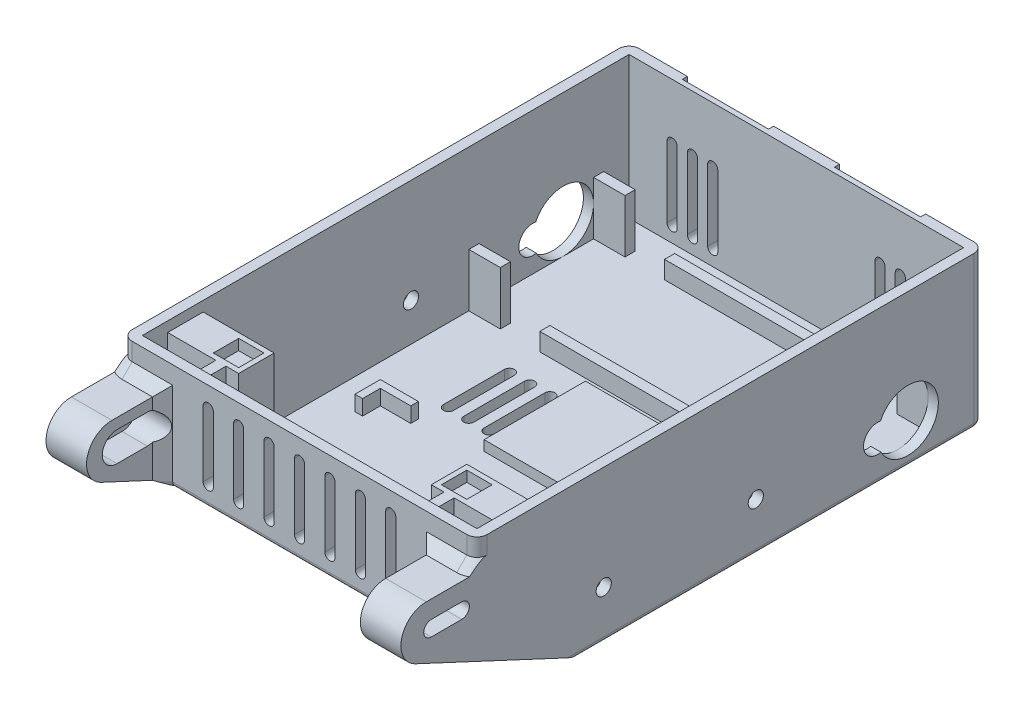
SolidWorks part; units mm, degrees
ref_plane "Ebene vorne" through (0, 0, 0) normal (0, 0, 1) x (1, 0, 0)
ref_plane "Ebene oben" through (0, 0, 0) normal (0, 1, 0) x (1, 0, 0)
ref_plane "Ebene rechts" through (0, 0, 0) normal (1, 0, 0) x (0, 0, -1)
sketch "Skizze1" plane through (0, 0, 0) normal (1, 0, 0) x (0, 0, -1)
  line L1 (-50, -15) -> (50, -15)
  line L2 (-50, -15) -> (-50, 15)
  line L3 (-50, 15) -> (50, 15)
  line L4 (50, -15) -> (50, 15)
  line L5 (-50, -15) -> (50, 15) construction
  line L6 (-50, 15) -> (50, -15) construction
  point P0 (0, 0)
  dimension "D1" = 100
  dimension "D2" = 30
extrude "Grundkörper" add sketch "Skizze1" along normal blind 70
sketch "Skizze2" plane through (70, 0, 0) normal (1, 0, 0) x (0, 0, -1)
  line L0 (-50, 15) -> (-50, -15) construction
  line L1 (50, 15) -> (-50, 15) construction
  line L2 (-30, -15) -> (-62.1124, -0.0319)
  line L3 (-50, -15) -> (50, -15) construction
  line L4 (-60, 9.5) -> (-50, 9.5)
  line L5 (-50, 9.5) -> (-50, -5.6777)
  circle A0 centre (-60, 4.5) radius 5
  line M5 (-50, 15) -> (-50, -15)
  dimension "D1" = 10
  dimension "D2" = 10
  dimension "D3" = 10.5
  dimension "D4" = 20
extrude "Nase_Kette" add sketch "Skizze2" against normal blind 3 contours A0 L2 L4 M5 | A0 region at (70, 2.3359, 53.3278) region at (70, 4.5, 60)
ref_plane "Ebene1" through (35, 0, 0) normal (1, 0, 0) x (0, 0, -1)
sketch "Skizze5" plane through (70, 0, 0) normal (1, 0, 0) x (0, 0, -1)
  line L0 (-50, -5.6777) -> (-30, -15)
  line L1 (-50, -15) -> (50, -15) construction
  line L2 (-30, -15) -> (-50, -15)
  line L3 (-50, -15) -> (-50, -5.6777)
  dimension "D1" = 20
extrude "Schnitt-Linear austragen2" cut sketch "Skizze5" against normal up to surface (70 mm away) up to face at (0, 0, 0)
mirror "Spiegeln2" about plane through (35, 0, 0) normal (1, 0, 0) of "Nase_Kette"
sketch "Skizze6" plane through (70, 0, 0) normal (1, 0, 0) x (0, 0, -1)
  line L0 (-53, 4.5) -> (-59, 4.5) construction
  line L1 (-53, 3) -> (-59, 3)
  line L2 (-53, 6) -> (-59, 6)
  line L6 (-50, 15) -> (-50, 9.5) construction
  line L7 (-60, 9.5) -> (-50, 9.5) construction
  arc A0 (-53, 3) -> (-53, 6) centre (-53, 4.5) ccw
  arc A1 (-59, 6) -> (-59, 3) centre (-59, 4.5) ccw
  point P2 (-56, 4.5)
  dimension "D1" = 1.5
  dimension "D2" = 3
  dimension "D3" = 6
  dimension "D4" = 5
extrude "Langloch_Nase" cut sketch "Skizze6" against normal up to surface (70 mm away) up to face at (0, 2.8308, 22.2768)
shell "Wandung1" thickness 2 removed face at (35, 15, 0)
sketch "Skizze7" plane through (70, 0, 0) normal (1, 0, 0) x (0, 0, -1)
  line L0 (-30, -15) -> (50, -15) construction
  line L1 (50, -15) -> (50, 15) construction
  circle A0 centre (35, -5.5) radius 1.5
  circle A1 centre (5, -5.5) radius 1.5
  circle A2 centre (-25, -5.5) radius 1.5
  dimension "D1" = 3
  dimension "D2" = 9.5
  dimension "D3" = 15
  dimension "D4" = 45
  dimension "D5" = 75
extrude "Bohrung_Räder" cut sketch "Skizze7" against normal up to surface (68 mm away)
mirror "Spiegeln3" about plane through (35, 0, 0) normal (1, 0, 0) of "Bohrung_Räder"
sketch "Skizze9" plane through (70, 0, 0) normal (1, 0, 0) x (0, 0, -1)
  line L0 (50, -15) -> (50, 15) construction
  line L2 (-30, -15) -> (50, -15) construction
  circle A0 centre (35, -7) radius 6
  circle A1 centre (35, -5.5) radius 1.5 construction
  circle A2 centre (29, -7.1) radius 2.75
  circle M1 centre (35, -5.5) radius 1.5
  dimension "D2" = 12
  dimension "D3" = 5.5
  dimension "D5" = 6
  dimension "D4" = 7.9
  dimension "D1" = 15
extrude "Aussparung_Servo" cut sketch "Skizze9" against normal up to surface (68 mm away) contours A2 A0 M1 | A0 A2 | A0 A2 region at (70, -7.1024, -35.5313) region at (70, -7.0788, -30.2733) region at (70, -7.1174, -27.9543)
mirror "Spiegeln4" about plane through (35, 0, 0) normal (1, 0, 0) of "Aussparung_Servo"
sketch "Skizze10" plane through (0, -13, 0) normal (0, 1, 0) x (1, 0, 0)
  line L0 (2, 35) -> (2, 48) construction
  line L1 (2, 41) -> (8.2, 41)
  line L2 (2, 41) -> (2, 43)
  line L3 (2, 43) -> (8.2, 43)
  line L4 (8.2, 41) -> (8.2, 43)
  line L5 (68, 48) -> (2, 48) construction
  line L6 (2, -29.5568) -> (2, 35) construction
  line L7 (2, 16.4) -> (8.2, 16.4)
  line L8 (2, 16.4) -> (2, 18.4)
  line L9 (2, 18.4) -> (8.2, 18.4)
  line L10 (8.2, 16.4) -> (8.2, 18.4)
  dimension "D1" = 5
  dimension "D2" = 2
  dimension "D3" = 6.2
  dimension "D4" = 2
  dimension "D5" = 22.6
  dimension "D6" = 6.2
extrude "Aufsatz-Linear austragen3" add sketch "Skizze10" along normal blind 10.5
sketch "Skizze12" plane through (0, -13, 0) normal (0, 1, 0) x (1, 0, 0)
  line L0 (35, -16.5) -> (35, 16.5) construction
  line L1 (54, 16.4) -> (16, 16.4)
  line L2 (54, 16.4) -> (54, 18.4)
  line L3 (54, 18.4) -> (16, 18.4)
  line L4 (16, 16.4) -> (16, 18.4)
  line L5 (54, 16.4) -> (16, 18.4) construction
  line L6 (54, 18.4) -> (16, 16.4) construction
  line L8 (2, 41) -> (8.2, 41) construction
  line L9 (54, 43) -> (16, 43)
  line L10 (54, 43) -> (54, 41)
  line L11 (54, 41) -> (16, 41)
  line L12 (16, 43) -> (16, 41)
  line L13 (54, 43) -> (16, 41) construction
  line L14 (54, 41) -> (16, 43) construction
  line L15 (8.2, 18.4) -> (2, 18.4) construction
  point P0 (35, 17.4)
  point P9 (35, 42)
  dimension "D1" = 38
  dimension "D2" = 38
  dimension "D3" = 2
  dimension "D4" = 2
  dimension "D5" = 22.6
  dimension "D6" = 22.6
extrude "Aufsatz-Linear austragen4" add sketch "Skizze12" along normal blind 3.5
mirror "Spiegeln5" about plane through (35, 0, 0) normal (1, 0, 0) of "Aufsatz-Linear austragen3"
sketch "Skizze13" plane through (0, -13, 0) normal (0, 1, 0) x (1, 0, 0)
  line L0 (35, -16.5) -> (35, 16.5) construction
  line L1 (42.5, -6.1) -> (27.5, -6.1)
  line L2 (42.5, -6.1) -> (42.5, 13.9)
  line L3 (42.5, 13.9) -> (27.5, 13.9)
  line L4 (27.5, -6.1) -> (27.5, 13.9)
  line L5 (42.5, -6.1) -> (27.5, 13.9) construction
  line L6 (42.5, 13.9) -> (27.5, -6.1) construction
  line L7 (16, 16.4) -> (54, 16.4) construction
  point P0 (35, 3.9)
  dimension "D1" = 20
  dimension "D2" = 15
  dimension "D3" = 2.5
extrude "Aufsatz-Linear austragen5" add sketch "Skizze13" along normal blind 2
sketch "Skizze14" plane through (0, -13, 0) normal (0, 1, 0) x (1, 0, 0)
  line L0 (8, -12.0568) -> (8, -7.0568)
  line L1 (8, -7.0568) -> (15.5, -7.0568)
  line L2 (15.5, -7.0568) -> (15.5, -8.5568)
  line L3 (15.5, -8.5568) -> (9.5, -8.5568)
  line L4 (9.5, -8.5568) -> (9.5, -12.0568)
  line L5 (9.5, -12.0568) -> (8, -12.0568)
  line L6 (8, -23.5568) -> (8, -28.5568)
  line L7 (8, -28.5568) -> (15.5, -28.5568)
  line L8 (15.5, -28.5568) -> (15.5, -27.0568)
  line L9 (15.5, -27.0568) -> (9.5, -27.0568)
  line L10 (9.5, -27.0568) -> (9.5, -23.5568)
  line L11 (9.5, -23.5568) -> (8, -23.5568)
  line L12 (2, -29.5568) -> (68, -29.5568) construction
  line L13 (2, -29.5568) -> (2, 16.4) construction
  dimension "D1" = 18.5
  dimension "D2" = 21
  dimension "D3" = 1.5
  dimension "D4" = 1.5
  dimension "D5" = 1.5
  dimension "D6" = 1.5
  dimension "D7" = 7.5
  dimension "D8" = 7.5
  dimension "D9" = 5
  dimension "D10" = 5
  dimension "D11" = 6
extrude "Aufsatz-Linear austragen6" add sketch "Skizze14" along normal blind 3
mirror "Spiegeln6" about plane through (35, 0, 0) normal (1, 0, 0) of "Aufsatz-Linear austragen6"
sketch "Skizze16" plane through (35, 0, 0) normal (1, 0, 0) x (0, 0, -1)
  line L0 (-43, -6.7339) -> (-36, -9.9967)
  line L2 (-29.5568, -13) -> (-48, -4.4033) construction
  line L3 (-36, -9.9967) -> (-36, 13.0033)
  line L4 (-36, 13.0033) -> (-43, 13.0033)
  line L5 (-43, 13.0033) -> (-43, -6.7339)
  line L6 (-48, 15) -> (-48, -4.4033) construction
  dimension "D1" = 5
  dimension "D2" = 7
  dimension "D3" = 23
extrude "Aufsatz-Linear austragen7" add sketch "Skizze16" against normal up to surface (33 mm away) from offset 19 up to face at (2, -5.5, 26.5) offset against normal yes
sketch "Skizze17" plane through (35, 0, 0) normal (1, 0, 0) x (0, 0, -1)
  line L0 (-43, -6.7339) -> (-48, -4.4033)
  line L1 (-48, -4.4033) -> (-48, 13.0033)
  line L2 (-48, 15) -> (-48, -4.4033) construction
  line L3 (-48, 13.0033) -> (-43, 13.0033)
  line L4 (-43, 13.0033) -> (-43, -6.7339)
extrude "Aufsatz-Linear austragen8" add sketch "Skizze17" against normal blind 2 from offset 21.5 offset against normal yes
sketch "Skizze18" plane through (0, 13.0033, 0) normal (0, 1, 0) x (1, 0, 0)
  line L0 (13.5, -43) -> (16, -43) construction
  line L1 (15, -42) -> (10, -42)
  line L2 (15, -42) -> (15, -37)
  line L3 (15, -37) -> (10, -37)
  line L4 (10, -42) -> (10, -37)
  line L5 (15, -42) -> (10, -37) construction
  line L6 (15, -37) -> (10, -42) construction
  line L7 (16, -36) -> (16, -43) construction
  point P0 (12.5, -39.5)
  dimension "D1" = 5
  dimension "D2" = 5
  dimension "D3" = 1
  dimension "D4" = 1
extrude "Schnitt-Linear austragen6" cut sketch "Skizze18" against normal blind 2.1
mirror "Spiegeln8" about plane through (35, 0, 0) normal (1, 0, 0) of "Schnitt-Linear austragen6", "Aufsatz-Linear austragen8", "Aufsatz-Linear austragen7"
sketch "Skizze21" plane through (0, 0, -50) normal (0, 0, -1) x (-1, 0, 0)
  line L0 (-28.5, 15) -> (-28.5, 13.3)
  line L1 (-70, 15) -> (0, 15) construction
  line L2 (-28.5, 13.3) -> (-30.5, 13.3)
  line L3 (-30.5, 13.3) -> (-30.5, 7)
  line L4 (-30.5, 7) -> (-9.5, 7)
  line L5 (-9.5, 7) -> (-9.5, 13.3)
  line L6 (-9.5, 13.3) -> (-11.5, 13.3)
  line L7 (-11.5, 13.3) -> (-11.5, 15)
  line L8 (-11.5, 15) -> (-28.5, 15)
  line L9 (-35, 16.5) -> (-35, -16.5) construction
  point P4 (-20, 15)
  dimension "D1" = 2
  dimension "D2" = 2
  dimension "D3" = 21
  dimension "D4" = 1.7
  dimension "D5" = 8
  dimension "D6" = 15
extrude "Schnitt-Linear austragen7" cut sketch "Skizze21" against normal blind 1
mirror "Spiegeln9" about plane through (35, 0, 0) normal (1, 0, 0) of "Schnitt-Linear austragen7"
sketch "Skizze22" plane through (0, 0, -50) normal (0, 0, -1) x (-1, 0, 0)
  line L0 (-55.5, 4) -> (-55.5, -10) construction
  line L1 (-54.5, 4) -> (-54.5, -10)
  line L2 (-56.5, 4) -> (-56.5, -10)
  line L3 (-60.5, 7) -> (-60.5, 13.3) construction
  line L4 (-14.5, 4) -> (-14.5, -10) construction
  line L5 (-13.5, 4) -> (-13.5, -10)
  line L6 (-15.5, 4) -> (-15.5, -10)
  line L8 (-39.5, 7) -> (-60.5, 7) construction
  line L9 (-30.5, 7) -> (-9.5, 7) construction
  line L10 (-9.5, 7) -> (-9.5, 13.3) construction
  arc A0 (-54.5, 4) -> (-56.5, 4) centre (-55.5, 4) ccw
  arc A1 (-56.5, -10) -> (-54.5, -10) centre (-55.5, -10) ccw
  arc A2 (-13.5, 4) -> (-15.5, 4) centre (-14.5, 4) ccw
  arc A3 (-15.5, -10) -> (-13.5, -10) centre (-14.5, -10) ccw
  point P2 (-55.5, -3)
  point P11 (-14.5, -3)
  dimension "D1" = 1
  dimension "D4" = 1
  dimension "D2" = 5
  dimension "D3" = 14
  dimension "D5" = 5
  dimension "D6" = 3
  dimension "D7" = 3
  dimension "D8" = 14
extrude "Schnitt-Linear austragen8" cut sketch "Skizze22" against normal up to surface (2 mm away) up to face at (35, 1, -48)
pattern_linear "Lineares Muster1" count 2 spacing 4 along (1, 0, 0) count 2 spacing 4 along (-1, 0, 0) of "Schnitt-Linear austragen8"
sketch "Skizze23" plane through (0, 0, 50) normal (0, 0, 1) x (1, 0, 0)
  line L0 (35, -2) -> (35, 11) construction
  line L1 (35, -16.5) -> (35, 16.5) construction
  line L2 (34, -2) -> (34, 11)
  line L3 (36, -2) -> (36, 11)
  line L4 (70, 15) -> (0, 15) construction
  arc A0 (34, -2) -> (36, -2) centre (35, -2) ccw
  arc A1 (36, 11) -> (34, 11) centre (35, 11) ccw
  point P4 (35, 4.5)
  dimension "D1" = 1
  dimension "D2" = 4
  dimension "D3" = 13
extrude "Schnitt-Linear austragen9" cut sketch "Skizze23" against normal up to surface (2 mm away) up to face at (35, 4.6328, 48)
pattern_linear "Lineares Muster2" count 4 spacing 6 along (-1, 0, 0) count 4 spacing 6 along (1, 0, 0) of "Schnitt-Linear austragen9"
sketch "Skizze24" plane through (0, -13, 0) normal (0, 1, 0) x (1, 0, 0)
  line L0 (24.5, -2.1) -> (24.5, 9.9) construction
  line L1 (23.5, -2.1) -> (23.5, 9.9)
  line L2 (25.5, -2.1) -> (25.5, 9.9)
  line L3 (27.5, 13.9) -> (27.5, -6.1) construction
  line L4 (42.5, 13.9) -> (27.5, 13.9) construction
  arc A0 (23.5, -2.1) -> (25.5, -2.1) centre (24.5, -2.1) ccw
  arc A1 (25.5, 9.9) -> (23.5, 9.9) centre (24.5, 9.9) ccw
  point P2 (24.5, 3.9)
  dimension "D1" = 1
  dimension "D2" = 2
  dimension "D3" = 12
  dimension "D4" = 10
extrude "Schnitt-Linear austragen10" cut sketch "Skizze24" against normal up to surface (2 mm away) up to face at (35, -15, -10)
pattern_linear "Lineares Muster3" count 3 spacing 4 along (-1, 0, 0) of "Schnitt-Linear austragen10"
sketch "Skizze25" plane through (0, -13, 0) normal (0, 1, 0) x (1, 0, 0)
  line L0 (45.5, -2.1) -> (45.5, 9.9) construction
  line L1 (44.5, -2.1) -> (44.5, 9.9)
  line L2 (46.5, -2.1) -> (46.5, 9.9)
  line L3 (42.5, 13.9) -> (27.5, 13.9) construction
  line L4 (42.5, -6.1) -> (42.5, 13.9) construction
  arc A0 (44.5, -2.1) -> (46.5, -2.1) centre (45.5, -2.1) ccw
  arc A1 (46.5, 9.9) -> (44.5, 9.9) centre (45.5, 9.9) ccw
  point P2 (45.5, 3.9)
  dimension "D1" = 1
  dimension "D2" = 10
  dimension "D3" = 12
  dimension "D4" = 2
extrude "Schnitt-Linear austragen11" cut sketch "Skizze25" against normal up to surface (2 mm away) up to face at (20.5, -15, -3.9)
pattern_linear "Lineares Muster4" count 3 spacing 4 along (1, 0, 0) of "Schnitt-Linear austragen11"
fillet "Verrundung1" radius 1 4 edges at (70, -15, -10) (35, -15, -50) (0, -15, -10) (35, -5.6777, 50)
fillet "Verrundung2" radius 2 6 edges at (69.7071, -14.7071, -49.7071) (0.2929, -14.7071, -49.7071) (70, 12.25, 50) (0, 12.25, 50) (0, 0.5, -50) (70, 0.5, -50)
sketch "Skizze26" plane through (67, 0, 0) normal (-1, 0, 0) x (0, 0, 1)
  line L0 (53, 4.5) -> (59, 4.5) construction
  line L1 (53, 7.4) -> (59, 7.4)
  line L2 (53, 1.6) -> (59, 1.6)
  line L3 (60, 9.5) -> (50, 9.5)
  line L4 (50, 9.5) -> (50, -5.0405)
  line L5 (49.4225, -5.9469) -> (62.1124, -0.0319)
  line L6 (60, 9.5) -> (50, 9.5)
  line L7 (50, 9.5) -> (50, -5.0405)
  line L8 (49.4225, -5.9469) -> (62.1124, -0.0319)
  arc A0 (53, 7.4) -> (53, 1.6) centre (53, 4.5) ccw
  arc A1 (59, 1.6) -> (59, 7.4) centre (59, 4.5) ccw
  arc A2 (49.4225, -5.9469) -> (50, -5.0405) centre (49, -5.0405) ccw
  arc A3 (62.1124, -0.0319) -> (60, 9.5) centre (60, 4.5) ccw
  arc A4 (49.4225, -5.9469) -> (50, -5.0405) centre (49, -5.0405) ccw
  arc A5 (62.1124, -0.0319) -> (60, 9.5) centre (60, 4.5) ccw
  point P11 (56, 4.5)
  dimension "D2" = 2.9
  dimension "D1" = 0
extrude "Aufsatz-Linear austragen9" add sketch "Skizze26" along normal blind 5
mirror "Spiegeln10" about plane through (35, 0, 0) normal (1, 0, 0) of "Aufsatz-Linear austragen9"
chamfer "Fase1" distance 2 angle 45 8 edges at (69.4142, 9.5, 49.4142) (62, -5.5778, 49.8433) (65, 9.5, 50) (62, 2.2298, 50) (0.5858, 9.5, 49.4142) (8, -5.5778, 49.8433) (5, 9.5, 50) (8, 2.2298, 50)
